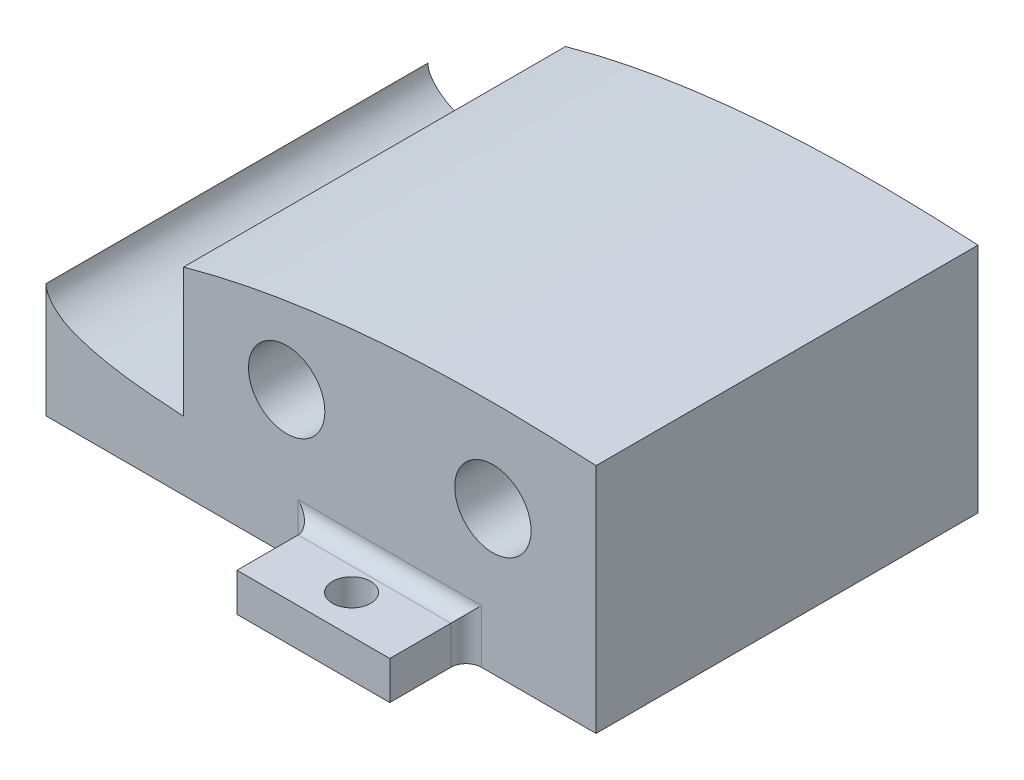
SolidWorks part; units mm, degrees
ref_plane "Front Plane" through (0, 0, 0) normal (0, 0, 1) x (1, 0, 0)
ref_plane "Top Plane" through (0, 0, 0) normal (0, 1, 0) x (1, 0, 0)
ref_plane "Right Plane" through (0, 0, 0) normal (1, 0, 0) x (0, 0, -1)
curve "Curve1"
  spline degree 3 poles (25.4, 0.033, 0) (24.9771, 0.1481, 0) (24.1334, 0.3778, 0) (22.4431, 0.7955, 0) (20.3293, 1.2569, 0) (17.7869, 1.7118, 0) (15.2464, 2.0846, 0) (12.7045, 2.3505, 0) (10.1628, 2.5164, 0) (8.041, 2.5181, 0) (6.3469, 2.4009, 0) (5.0745, 2.2465, 0) (3.7995, 2.0188, 0) (2.7428, 1.745, 0) (1.8961, 1.4685, 0) (1.2577, 1.2074, 0) (0.7129, 0.9251, 0) (0.2401, 0.5874, 0) (-0.1715, 0.0442, 0) (0.2727, -0.3711, 0) (0.7261, -0.5342, 0) (1.266, -0.6443, 0) (1.9036, -0.7002, 0) (2.7513, -0.7398, 0) (3.8103, -0.7368, 0) (5.0806, -0.7013, 0) (6.3499, -0.6336, 0) (8.0433, -0.5544, 0) (10.1596, -0.4528, 0) (12.7001, -0.3574, 0) (15.2397, -0.2514, 0) (17.7796, -0.1611, 0) (20.3198, -0.0947, 0) (22.4366, -0.061, 0) (24.13, -0.0388, 0) (24.9767, -0.035, 0) (25.4, -0.033, 0) knots 0 0 0 0 0.025305 0.050488 0.10052 0.150191 0.199587 0.24874 0.297716 0.346601 0.371103 0.395726 0.42057 0.445825 0.458702 0.47192 0.485786 0.493461 0.506863 0.516148 0.522766 0.535269 0.547551 0.559786 0.584229 0.608681 0.633151 0.657622 0.706558 0.755482 0.804406 0.85332 0.902221 0.951113 0.975557 1 1 1 1
sketch "Original NACA 4412" plane through (0, 0, 0) normal (0, 0, 1) x (1, 0, 0)
  line L0 (25.4, 0.033) -> (25.4, -0.033)
  spline S0 degree 3 poles (623.3011, 1907.6527) (79.6214, -43.1606) (55.117, -7.2775) (22.4431, 0.7955) (20.3293, 1.2569) (17.7869, 1.7118) (15.2464, 2.0846) (12.7045, 2.3505) (10.1628, 2.5164) (8.041, 2.5181) (6.3469, 2.4009) (5.0745, 2.2465) (3.7995, 2.0188) (2.7428, 1.745) (1.8961, 1.4685) (1.2577, 1.2074) (0.7129, 0.9251) (0.2401, 0.5874) (-0.1715, 0.0442) (0.2727, -0.3711) (0.7261, -0.5342) (1.266, -0.6443) (1.9036, -0.7002) (2.7513, -0.7398) (3.8103, -0.7368) (5.0806, -0.7013) (6.3499, -0.6336) (8.0433, -0.5544) (10.1596, -0.4528) (12.7001, -0.3574) (15.2397, -0.2514) (17.7796, -0.1611) (20.3198, -0.0947) (22.4366, -0.061) (67.8901, 0.5348) (112.6717, -18.929) (139.2928, 1995.2022) knots -1.842584 -1.842584 -1.842584 -1.842584 0.025305 0.050488 0.10052 0.150191 0.199587 0.24874 0.297716 0.346601 0.371103 0.395726 0.42057 0.445825 0.458702 0.47192 0.485786 0.493461 0.506863 0.516148 0.522766 0.535269 0.547551 0.559786 0.584229 0.608681 0.633151 0.657622 0.706558 0.755482 0.804406 0.85332 0.902221 0.951113 0.975557 3.526814 3.526814 3.526814 3.526814 only from (25.4, 0.033) to (25.4, -0.033) construction
  spline S1 degree 3 poles (25.4, 0.033) (24.9771, 0.1481) (24.1334, 0.3778) (22.4431, 0.7955) (20.3293, 1.2569) (17.7869, 1.7118) (15.2464, 2.0846) (12.7045, 2.3505) (10.1628, 2.5164) (8.041, 2.5181) (6.3469, 2.4009) (5.0745, 2.2465) (3.7995, 2.0188) (2.7428, 1.745) (1.8961, 1.4685) (1.2577, 1.2074) (0.7129, 0.9251) (0.2401, 0.5874) (-0.1715, 0.0442) (0.2727, -0.3711) (0.7261, -0.5342) (1.266, -0.6443) (1.9036, -0.7002) (2.7513, -0.7398) (3.8103, -0.7368) (5.0806, -0.7013) (6.3499, -0.6336) (8.0433, -0.5544) (10.1596, -0.4528) (12.7001, -0.3574) (15.2397, -0.2514) (17.7796, -0.1611) (20.3198, -0.0947) (22.4366, -0.061) (24.13, -0.0388) (24.9767, -0.035) (25.4, -0.033) knots 0 0 0 0 0.025305 0.050488 0.10052 0.150191 0.199587 0.24874 0.297716 0.346601 0.371103 0.395726 0.42057 0.445825 0.458702 0.47192 0.485786 0.493461 0.506863 0.516148 0.522766 0.535269 0.547551 0.559786 0.584229 0.608681 0.633151 0.657622 0.706558 0.755482 0.804406 0.85332 0.902221 0.951113 0.975557 1 1 1 1
sketch "Scaled and rotated by 1.5°" plane through (0, 0, 0) normal (0, 0, 1) x (1, 0, 0)
  line L0 (228.6156, -6.2198) -> (228.6, -6.8141)
  line L1 (40.005, 17.5068) -> (40.005, -8.0377) construction
  line L2 (0, 2.8493) -> (0, 0) construction
  line L3 (40.005, 4.7346) -> (74.295, 4.7346) construction
  line L4 (74.295, 4.7346) -> (40.005, 4.7346) construction
  line L5 (228.6, -6.8141) -> (228.6, -6.2434) construction
  circle A0 centre (40.005, 4.7346) radius 6.35
  circle A1 centre (74.295, 4.7346) radius 6.35
  spline S1 degree 3 poles (228.6156, -6.2198) (224.8373, -5.0843) (217.299, -2.8187) (202.1877, 1.3376) (183.276, 5.9878) (160.5054, 10.6799) (137.7331, 14.6335) (114.9229, 17.6255) (92.0911, 19.717) (72.9986, 20.2321) (57.7264, 19.5766) (46.2411, 18.4872) (34.7139, 16.739) (25.1416, 14.5242) (17.4573, 12.2353) (11.6508, 10.0367) (6.6824, 7.6245) (2.3479, 4.6971) (-1.484, -0.0934) (2.416, -3.9359) (6.457, -5.51) (11.2894, -6.6275) (17.0139, -7.2813) (24.6323, -7.8374) (34.1618, -8.0602) (45.6007, -8.0396) (57.039, -7.7297) (72.295, -7.4161) (91.3623, -7.0002) (114.245, -6.7401) (137.1228, -6.385) (159.999, -6.1713) (182.8715, -6.1724) (201.9277, -6.3679) (217.1704, -6.5672) (224.7902, -6.7318) (228.6, -6.8141) knots 0 0 0 0 0.025305 0.050488 0.10052 0.150191 0.199587 0.24874 0.297716 0.346601 0.371103 0.395726 0.42057 0.445825 0.458702 0.47192 0.485786 0.493461 0.506863 0.516148 0.522766 0.535269 0.547551 0.559786 0.584229 0.608681 0.633151 0.657622 0.706558 0.755482 0.804406 0.85332 0.902221 0.951113 0.975557 1 1 1 1
  dimension "D2" = 12.7
  dimension "D1" = 40.005
  dimension "D3" = 34.29
  dimension "D5" = 228.6
  dimension "D4" = 1.5
sketch "Sketch6" plane through (0, 0, 0) normal (0, 0, 1) x (1, 0, 0)
  line L1 (40.005, 17.5068) -> (40.005, -8.0377) construction
  line L2 (0, 2.2821) -> (0, 0) construction
  line L3 (40.005, 4.7346) -> (74.295, 4.7346) construction
  line L4 (74.295, 4.7346) -> (40.005, 4.7346) construction
  line L6 (0, 0) -> (0, -19.05)
  line L7 (0, -19.05) -> (91.44, -19.05)
  line L8 (91.44, -19.05) -> (91.44, 19.5089)
  line L9 (22.86, -7.6743) -> (22.86, 13.8098)
  circle A0 centre (40.005, 4.7346) radius 6.35
  circle A1 centre (74.295, 4.7346) radius 6.35
  spline S0 degree 3 poles (0, 0) (0, -0.1787) (0.1349, -1.6884) (2.416, -3.9359) (6.457, -5.51) (11.2894, -6.6275) (17.0139, -7.2813) (20.8709, -7.5628) (22.818, -7.672) (22.86, -7.6743) knots 0.505626 0.505626 0.505626 0.505626 0.506863 0.516148 0.522766 0.535269 0.547551 0.559786 0.560056 0.560056 0.560056 0.560056
  spline S2 degree 3 poles (91.44, 19.5089) (84.0356, 19.9341) (72.792, 20.2232) (57.7264, 19.5766) (46.2411, 18.4872) (34.7139, 16.739) (26.9508, 14.9428) (23.0064, 13.8507) (22.86, 13.8098) knots 0.299041 0.299041 0.299041 0.299041 0.346601 0.371103 0.395726 0.42057 0.445825 0.446799 0.446799 0.446799 0.446799
  dimension "D2" = 12.7
  dimension "D1" = 40.005
  dimension "D3" = 34.29
  dimension "D6" = 91.44
  dimension "D7" = 22.86
  dimension "D4" = 19.05
extrude "Boss-Extrude2" add sketch "Sketch6" along normal blind 31.75 and the other way blind 31.75
sketch "Sketch7" plane through (0, -19.05, 0) normal (0, -1, 0) x (1, 0, 0)
  line L0 (0, 31.75) -> (91.44, 31.75) construction
  line L1 (44.45, 31.75) -> (69.85, 31.75)
  line L2 (44.45, 31.75) -> (44.45, 44.45)
  line L3 (44.45, 44.45) -> (69.85, 44.45)
  line L4 (69.85, 31.75) -> (69.85, 44.45)
  line L5 (57.15, 44.45) -> (57.15, 31.75) construction
  line L6 (0, 0) -> (35.4889, 0) construction
  line L7 (57.15, -44.45) -> (57.15, -31.75) construction
  line L8 (69.85, -31.75) -> (69.85, -44.45)
  line L9 (44.45, -44.45) -> (69.85, -44.45)
  line L10 (44.45, -31.75) -> (44.45, -44.45)
  line L11 (44.45, -31.75) -> (69.85, -31.75)
  circle A0 centre (57.15, 38.1) radius 3.175
  circle A1 centre (57.15, -38.1) radius 3.175
  point P6 (57.15, 44.45)
  dimension "D2" = 12.7
  dimension "D4" = 6.35
  dimension "D1" = 57.15
  dimension "D5" = 38.1
extrude "Boss-Extrude3" add sketch "Sketch7" against normal blind 6.35
fillet "Fillet2" radius 2.54 6 edges at (57.15, -12.7, 31.75) (44.45, -15.875, 31.75) (69.85, -15.875, 31.75) (57.15, -12.7, -31.75) (69.85, -15.875, -31.75) (44.45, -15.875, -31.75)
equation "\"span\" = 48"
equation "\"wing_chord\"= 9"
equation "\"fuse_len\"= 15"
equation "\"fuse_height\"= 5"
equation "\"fuse_wid\"= 5"
equation "\"foam_t\"= 0.1875"
equation "\"main_spar_len\"= 36"
equation "\"x_fuse_to_wing\"= 3"
equation "\"x_cg_from_le\"= 2.25"
equation "\"boom_len\"= 36"
equation "\"wing_angle\"= 1.5"
equation "\"boom_d\"= 0.75"
equation "\"wing_spar_d\"= 0.5"
equation "\"wing_spar_l\"= 48"
equation "\"wing_spar_spacing\"= 1.35"
equation "\"wing_mount_l\" = 2.5"
equation "\"vstab_span\"= 6.5"
equation "\"hstab_span\"= 15.25"
equation "\"tail_chord\"= 5"
equation "\"D1@Scaled and rotated by 1.5°\"= \"x_cg_from_le\" - \"wing_spar_spacing\"/2"
equation "\"D2@Scaled and rotated by 1.5°\"= \"wing_spar_d\""
equation "\"D3@Scaled and rotated by 1.5°\"=\"wing_spar_spacing\""
equation "\"D5@Scaled and rotated by 1.5°\"= \"wing_chord\""
equation "\"D3@Sketch6\"= \"wing_spar_spacing\""
equation "\"D1@Sketch6\"=\"x_cg_from_le\" - \"wing_spar_spacing\"/2"
equation "\"D6@Sketch6\"= \"wing_chord\"*0.4"
equation "\"D7@Sketch6\"= \"x_cg_from_le\"-\"wing_spar_spacing\""
equation "\"D1@Sketch7\"= \"x_cg_from_le\""
equation "\"wing_mount_l\"= 2.5"
equation "\"D2@Boss-Extrude2\"= \"wing_mount_l\"/2"
equation "\"D1@Boss-Extrude2\"= \"wing_mount_l\"/2"
equation "\"wing_mount_bolt_spacing\"= \"wing_mount_l\" + 0.5"
equation "\"boom_mount_l\"= 1"
equation "\"D5@Sketch7\"= \"wing_mount_bolt_spacing\"/2"
